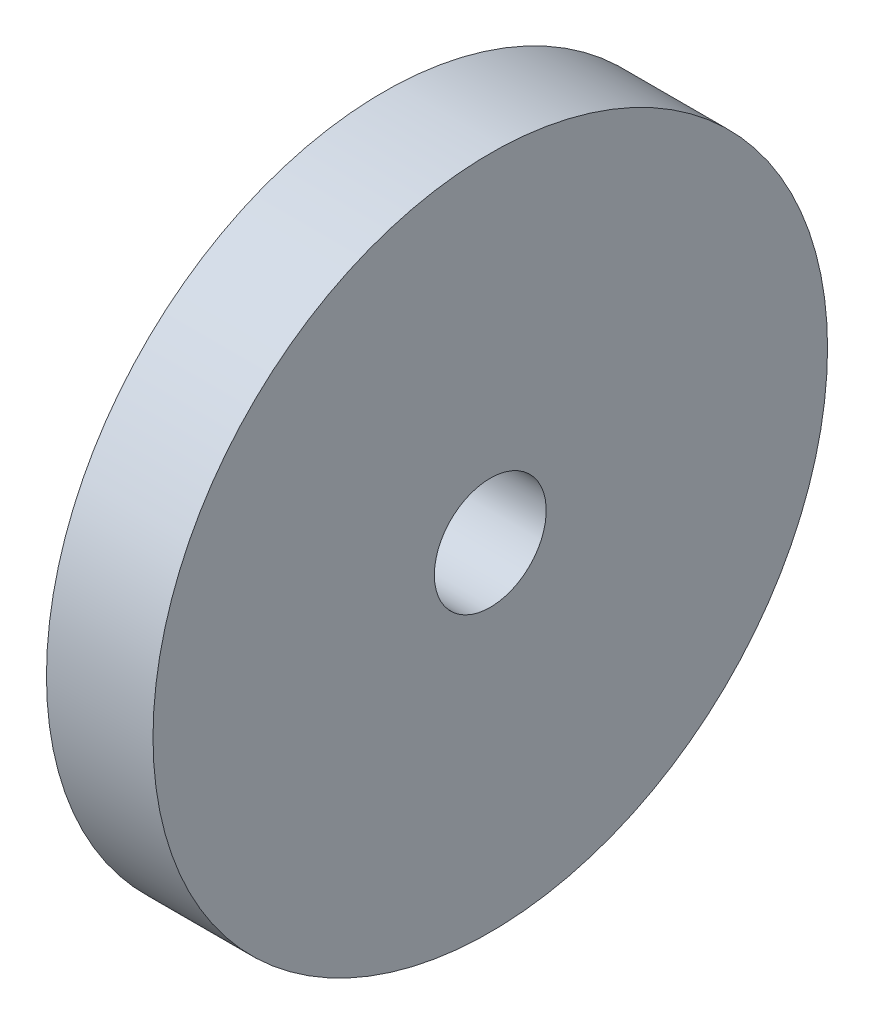
SolidWorks part; units mm, degrees
ref_plane "Front Plane" through (0, 0, 0) normal (0, 0, 1) x (1, 0, 0)
ref_plane "Top Plane" through (0, 0, 0) normal (0, 1, 0) x (1, 0, 0)
ref_plane "Right Plane" through (0, 0, 0) normal (1, 0, 0) x (0, 0, -1)
ref_axis "Axis1" through (-314.8, 32.815, -139.7) along (1, 0, 0)
ref_plane "Plane1" through (0, 32.815, 0) normal (0, -1, 0) x (1, 0, 0)
sketch "Sketch2" plane through (0, 32.815, 0) normal (0, -1, 0) x (1, 0, 0)
  line L0 (-314.8, -144.5) -> (-304.8, -144.5) construction
  line L1 (-314.7409, -144.754) -> (-305.1122, -144.754)
  line L2 (-314.7409, -144.754) -> (-314.7409, -170.18)
  line L3 (-314.7409, -170.18) -> (-305.1122, -170.18)
  line L4 (-305.1122, -144.754) -> (-305.1122, -170.18)
  line L5 (-314.8, -134.9) -> (-314.8, -144.5) construction
  line L6 (-304.8, -134.9) -> (-314.8, -134.9) construction
  line L7 (-314.8, -134.9) -> (-314.8, -144.5) construction
  line L8 (-304.8, -134.9) -> (-314.8, -134.9)
  line L9 (-332.2066, -139.7) -> (-314.8, -139.7) construction
  dimension "D1" = 0.254
  dimension "1.2" = 30.48
revolve "Revolve1" add sketch "Sketch2" angle 360 about L9
